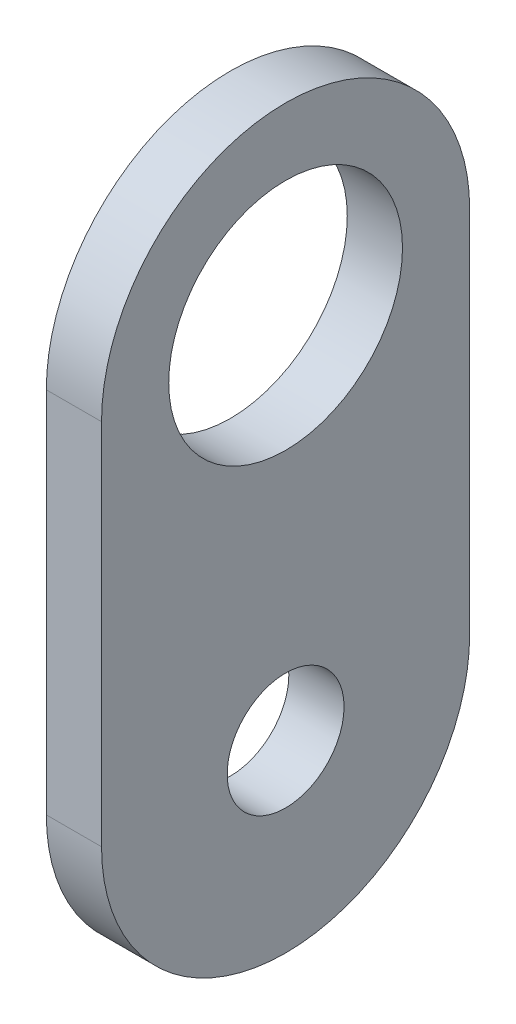
SolidWorks part; units mm, degrees
material "Acrylic (Medium-high impact)"
ref_plane "Alzado" through (0, 0, 0) normal (0, 0, 1) x (1, 0, 0)
ref_plane "Planta" through (0, 0, 0) normal (0, 1, 0) x (1, 0, 0)
ref_plane "Vista lateral" through (0, 0, 0) normal (1, 0, 0) x (0, 0, -1)
sketch "Sketch3" plane through (0, 0, 0) normal (1, 0, 0) x (0, 0, -1)
  line L1 (-10, -20) -> (10, -20)
  line L2 (-10, -20) -> (-10, 20)
  line L3 (-10, 20) -> (10, 20)
  line L4 (10, -20) -> (10, 20)
  line L5 (-10, -20) -> (10, 20) construction
  line L6 (-10, 20) -> (10, -20) construction
  point P0 (0, 0)
  dimension "D1" = 40
  dimension "D2" = 20
extrude "Boss-Extrude1" add sketch "Sketch3" along normal blind 3 contours L3 L4 L1 L2
sketch "Sketch4" plane through (3, 0, 0) normal (1, 0, 0) x (0, 0, -1)
  line L0 (0, 0) -> (0, -20) construction
  line L1 (-10, -20) -> (10, -20) construction
  line L2 (0, 0) -> (0, 20) construction
  line L3 (-10, 20) -> (10, 20) construction
  line L4 (0, 0) -> (0, 10) construction
  line L5 (0, 0) -> (0, -10) construction
  line L6 (0, 0) -> (0, -8.5) construction
  line L7 (0, 10) -> (0, -8.5) construction
  circle A0 centre (0, 10) radius 6.35
  circle A1 centre (0, -10) radius 3.175
  dimension "D3" = 6.35
  dimension "D4" = 12.7
  dimension "D1" = 10
  dimension "D2" = 10
extrude "Cut-Extrude1" cut sketch "Sketch4" against normal blind 5
fillet "Fillet2" 2 edges at (1.5, -20, -10) (1.5, -20, 10) type full round first side face at (1.5, 0, -10) second side face at (1.5, 0, 10) middle face at (1.5, -20, 0)
fillet "Fillet3" 2 edges at (1.5, 20, -10) (1.5, 20, 10) type full round first side face at (1.5, 5, -10) second side face at (1.5, 5, 10) middle face at (1.5, 20, 0)
